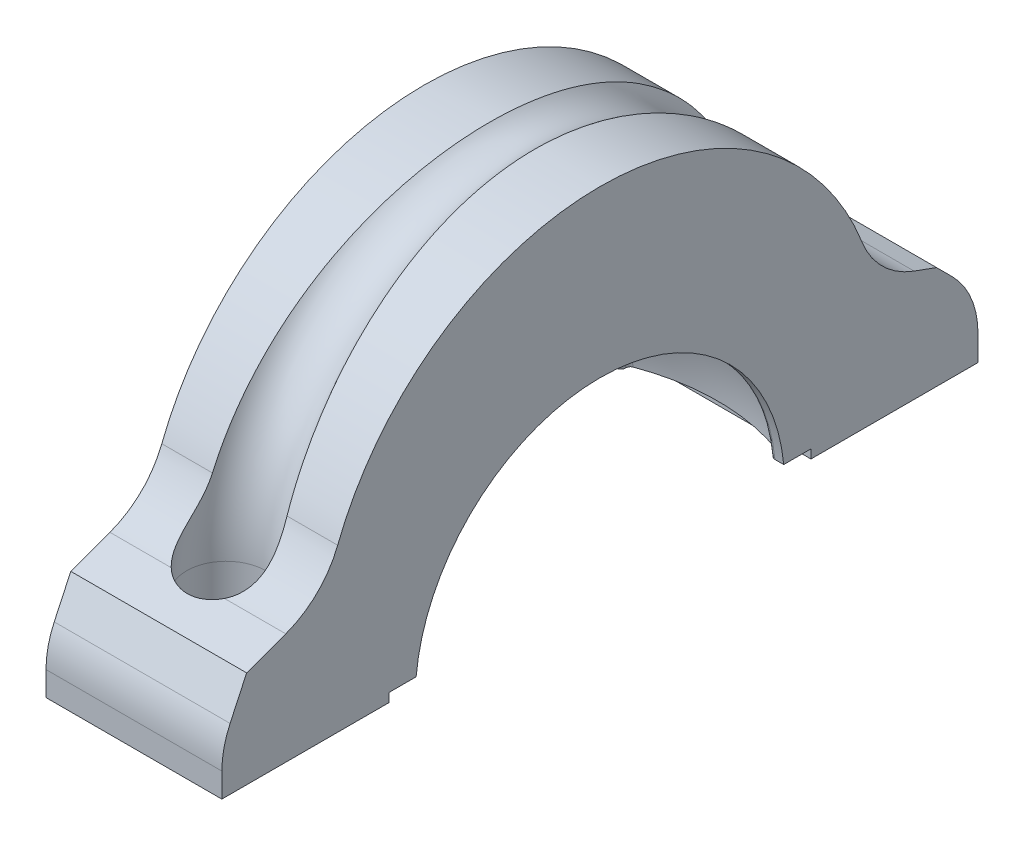
SolidWorks part; units mm, degrees
ref_plane "Front Plane" through (0, 0, 0) normal (0, 0, 1) x (1, 0, 0)
ref_plane "Top Plane" through (0, 0, 0) normal (0, 1, 0) x (1, 0, 0)
ref_plane "Right Plane" through (0, 0, 0) normal (1, 0, 0) x (0, 0, -1)
sketch "Sketch1" plane through (0, 0, 0) normal (1, 0, 0) x (0, 0, -1)
  line L0 (-86, 0) -> (-67, 0)
  line L1 (0, 0) -> (0, 10)
  line L2 (0, 10) -> (-11.8895, 14.3274)
  line L3 (-43, 17.5) -> (-43, 45.3769) construction
  line L4 (-86, 0) -> (-86, 10)
  line L5 (-86, 10) -> (-74.1105, 14.3274)
  line L6 (-19, 0) -> (-19, 1)
  line L8 (-67, 0) -> (-67, 1)
  line L10 (-19, 0) -> (0, 0)
  line L11 (-67, 1) -> (-19, 1)
  line L12 (-67, 0) -> (-19, 0) construction
  arc A1 (-74.1105, 14.3274) -> (-11.8895, 14.3274) centre (-43, 6.835) cw
  dimension "D1" = 32
  dimension "D2" = 86
  dimension "D3" = 10
  dimension "D4" = 70
  dimension "D6" = 1
  dimension "D8" = 19
  dimension "D9" = 43
extrude "Boss-Extrude1" add sketch "Sketch1" along normal blind 20
fillet "Fillet1" radius 10 2 edges at (10, 14.3274, 11.8895) (10, 14.3274, 74.1105)
chamfer "Chamfer1" distance 3 angle 45 2 edges at (10, 10, 0) (10, 10, 86) first distance on face at (10, 5, 0) first distance on face at (10, 11.3231, 82.3648)
fillet "Fillet2" [suppressed] radius 1
fillet "Fillet3" [suppressed] radius 1
ref_plane "Plane1" through (10, 0, 0) normal (1, 0, 0) x (0, 0, -1)
sketch "Sketch2" plane through (10, 0, 0) normal (1, 0, 0) x (0, 0, -1)
  line L1 (-10.5, -11.403) -> (-10.5, 10)
  line L4 (-43, -11.403) -> (-43, 46.1538) construction
  line L5 (-75.5, -11.403) -> (-75.5, 10)
  line L7 (-67, 1) -> (-19, 1) construction
  line L8 (-19, 0) -> (0, 0) construction
  arc A1 (-75.5, 10) -> (-10.5, 10) centre (-43, 10) cw
  point P12 (-43, 1)
  dimension "D2" = 32.5
  dimension "D1" = 65
  dimension "D3" = 10
ref_plane "Plane4" through (0, 0, 86) normal (0, 0, -1) x (-1, 0, 0)
ref_plane "Plane5" through (0, -11.403, 0) normal (0, -1, 0) x (-1, 0, 0)
sketch "Sketch5" plane through (0, -11.403, 0) normal (0, -1, 0) x (-1, 0, 0)
  circle A0 centre (-10, -10.5) radius 4.5
  dimension "D1" = 9
sweep "augu cut" cut profiles "Sketch5" path "Sketch2"
ref_plane "laagri center " through (0, -1, 0) normal (0, -1, 0) x (-1, 0, 0)
sketch "Sketch6" plane through (0, -1, 0) normal (0, -1, 0) x (1, 0, 0)
  line L0 (0, 64) -> (1.5, 64)
  line L2 (1.5, 64.9089) -> (1.5, 64)
  line L3 (0, 43) -> (20, 43)
  line L4 (18.5, 64.9089) -> (18.5, 64)
  line L5 (10, 10.5) -> (10, 75.5) construction
  line L7 (0, 67) -> (0, 19) construction
  line L8 (18.5, 64) -> (20, 64)
  line L9 (20, 67) -> (20, 19) construction
  line L10 (0, 64) -> (0, 43)
  line L12 (20, 64) -> (20, 43)
  arc A0 (1.5, 64.9089) -> (18.5, 64.9089) centre (10, 43) cw
  point P0 (10.2498, 50.9501)
  point P6 (10, 66.5)
  dimension "D2" = 23.5
  dimension "D1" = 17
  dimension "D3" = 21
  dimension "D4" = 1.5
  dimension "D5" = 1.5
  dimension "D6" = 0.9089
revolve "Cut-Revolve2" cut sketch "Sketch6" angle 360 about L3
sketch "Sketch8" plane through (0, -1, 0) normal (0, -1, 0) x (-1, 0, 0)
  line L0 (-30.4774, -7.5) -> (-30.4774, -72.5) construction
  line L3 (-30.4774, -40) -> (16.6094, -40) construction
fillet "Fillet4" radius 10 2 edges at (10, 4.9805, 86) (10, 7, 0)
fillet "Fillet5" radius 0.5 4 edges at (1.5, 20.9089, 43) (1.5, 20, 43) (18.5, 20, 43) (18.5, 20.9089, 43)
